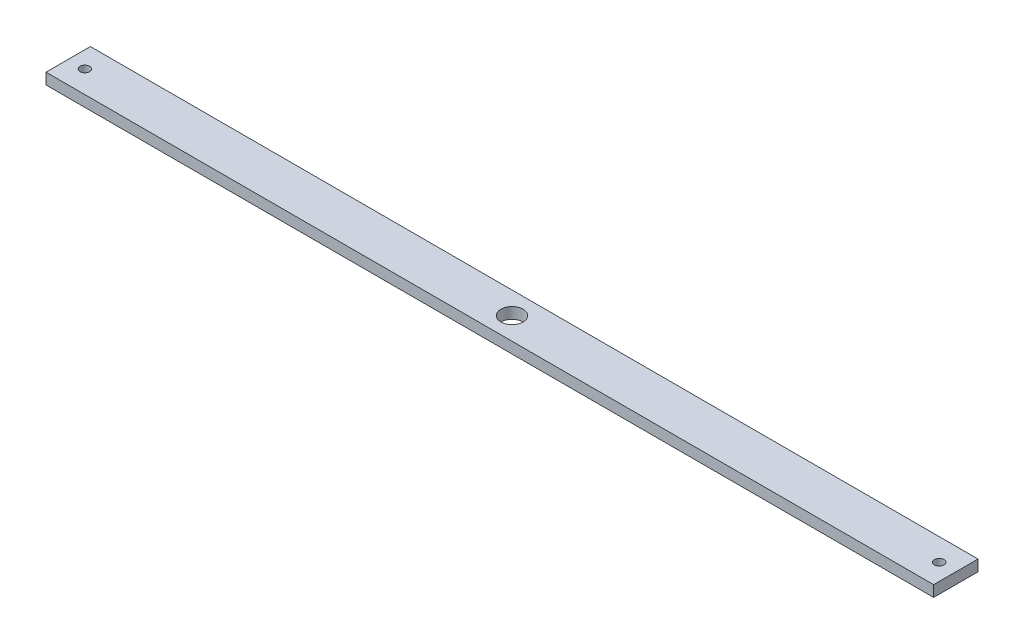
SolidWorks part; units mm, degrees
ref_plane "Front Plane" through (0, 0, 0) normal (0, 0, 1) x (1, 0, 0)
ref_plane "Top Plane" through (0, 0, 0) normal (0, 1, 0) x (1, 0, 0)
ref_plane "Right Plane" through (0, 0, 0) normal (1, 0, 0) x (0, 0, -1)
sketch "Sketch1" plane through (0, 0, 0) normal (0, 1, 0) x (1, 0, 0)
  line L1 (-254, -12.7) -> (254, -12.7)
  line L2 (-254, -12.7) -> (-254, 12.7)
  line L3 (-254, 12.7) -> (254, 12.7)
  line L4 (254, -12.7) -> (254, 12.7)
  line L5 (-254, -12.7) -> (254, 12.7) construction
  line L6 (-254, 12.7) -> (254, -12.7) construction
  point P0 (0, 0)
  dimension "D1" = 508
  dimension "D2" = 25.4
extrude "Boss-Extrude1" add sketch "Sketch1" along normal blind 6.35
hole_wizard "1/4-28 Tapped Hole1" positions "Sketch3" profile "Sketch4" tap size "1/4-28" standard "ANSI Inch" end condition through all
sketch "Sketch3" plane through (0, 6.35, 0) normal (0, 1, 0) x (1, 0, 0)
  line L0 (-254, 0) -> (-244.475, 0) construction
  line L1 (-254, 12.7) -> (-254, -12.7) construction
  line L4 (254, 0) -> (244.475, 0) construction
  line L5 (254, -12.7) -> (254, 12.7) construction
  point P2 (-244.475, 0)
  point P10 (244.475, 0)
  dimension "D1" = 9.525
sketch "Sketch4" plane through (-244.475, 6.35, 0) normal (1, 0, 0) x (0, 0, 1)
  line L0 (0, 0) -> (0, 6.35)
  line L1 (0, 6.35) -> (2.7051, 6.35)
  line L2 (2.7051, 6.35) -> (2.7051, 0)
  line L5 (2.7051, 0) -> (0, 0)
  line L11 (0, -6.35) -> (0, 107.95) construction
  dimension "Thread Major Dia." = 5.4102
  dimension "Thru Tap Drill Depth" = 6.35
sketch "Sketch5" plane through (0, 6.35, 0) normal (0, 1, 0) x (1, 0, 0)
  circle A0 centre (0, 0) radius 6.35
  dimension "D1" = 12.7
extrude "Cut-Extrude1" cut sketch "Sketch5" against normal through all
